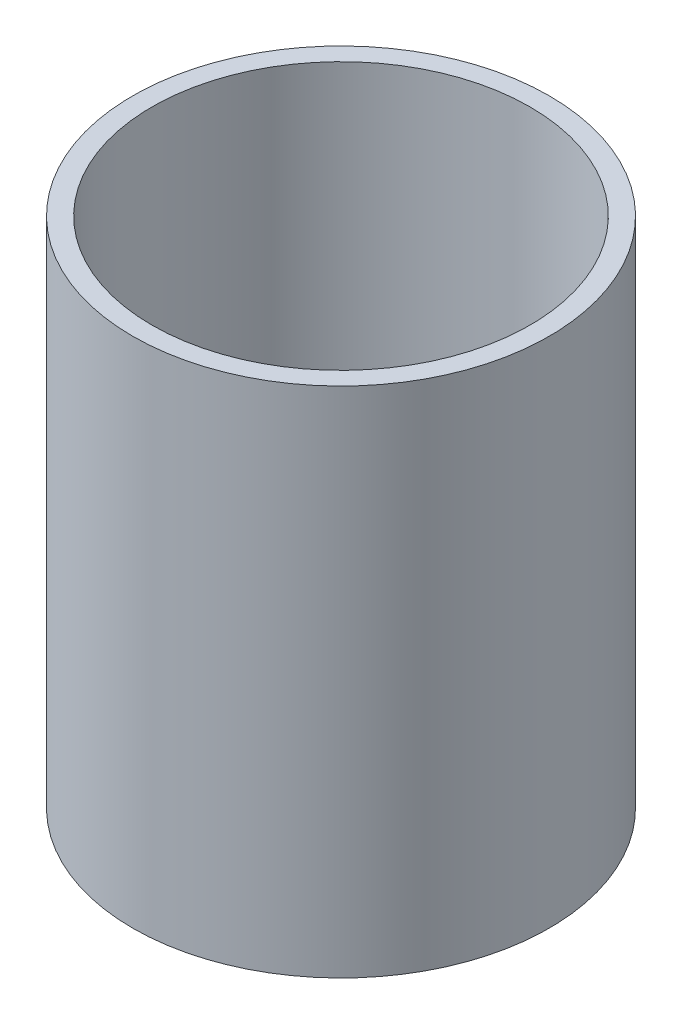
SolidWorks part; units mm, degrees
ref_plane "Front Plane" through (0, 0, 0) normal (0, 0, 1) x (1, 0, 0)
ref_plane "Top Plane" through (0, 0, 0) normal (0, 1, 0) x (1, 0, 0)
ref_plane "Right Plane" through (0, 0, 0) normal (1, 0, 0) x (0, 0, -1)
sketch "Sketch1" plane through (0, 0, 0) normal (0, 1, 0) x (1, 0, 0)
  circle A1 centre (0, 0) radius 82.55
  dimension "D1" = 165.1
extrude "Boss-Extrude1" add sketch "Sketch1" along normal blind 203.2
sketch "Sketch2" plane through (0, 203.2, 0) normal (0, 1, 0) x (1, 0, 0)
  circle A1 centre (0, 0) radius 74.93
  circle A2 centre (0, 0) radius 74.93
  dimension "D1" = 7.62
extrude "Cut-Extrude1" cut sketch "Sketch2" against normal blind 203.2
sketch "Sketch3" plane through (0, 0, 0) normal (1, 0, 0) x (0, 0, -1)
  circle A0 centre (0, 101.6) radius 6.35
  dimension "D1" = 12.7
extrude "Cut-Extrude3" cut sketch "Sketch3" against normal blind 115.57
